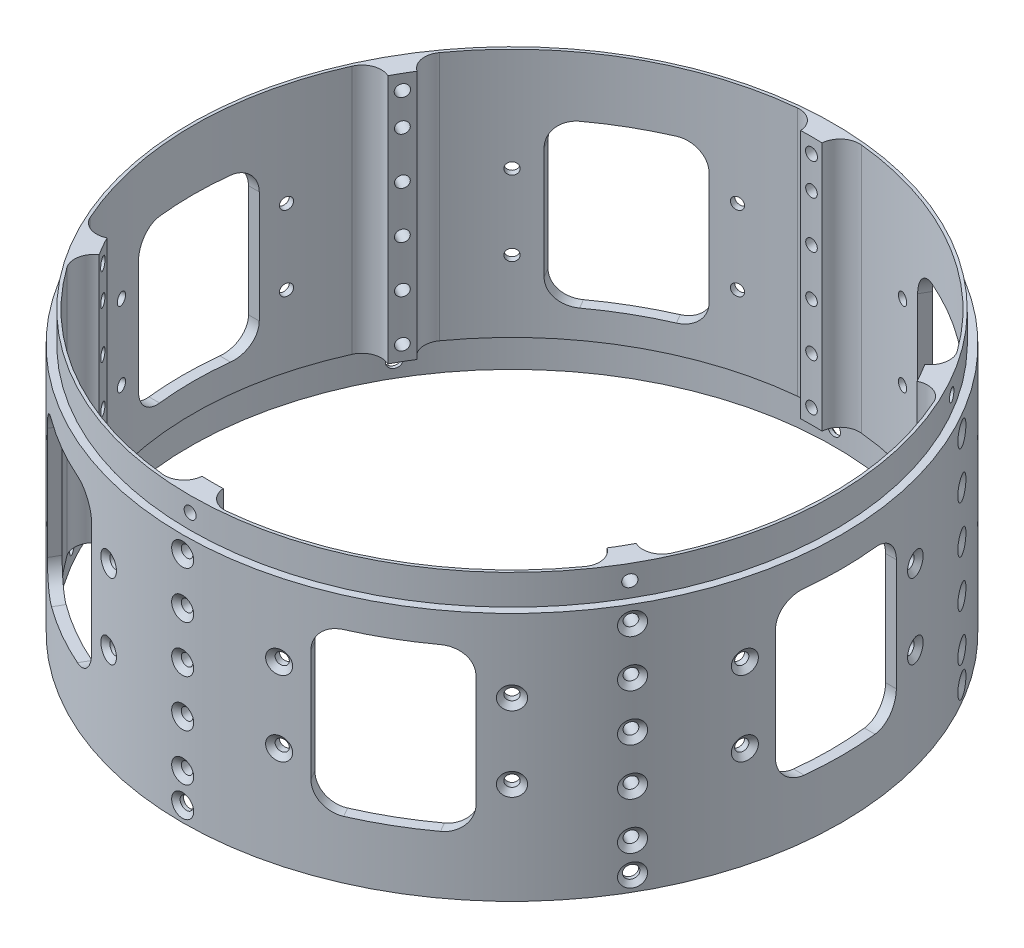
SolidWorks part; units mm, degrees
material "6061-T6 (SS)"
ref_plane "Front Plane" through (0, 0, 0) normal (0, 0, 1) x (1, 0, 0)
ref_plane "Top Plane" through (0, 0, 0) normal (0, 1, 0) x (1, 0, 0)
ref_plane "Right Plane" through (0, 0, 0) normal (1, 0, 0) x (0, 0, -1)
sketch "Sketch1" plane through (0, 0, 0) normal (0, 0, 1) x (1, 0, 0)
  line L0 (0, 42.3951) -> (0, -32.8937) construction
  line L1 (0, -35.6235) -> (0, 35.6235) construction
  line L2 (76.2, -63.5) -> (76.2, 0)
  line L3 (76.2, 0) -> (81.8896, 0)
  line L4 (81.8896, 0) -> (81.8896, -7.6708)
  line L5 (81.8896, -7.6708) -> (83.82, -7.6708)
  line L6 (83.82, -7.6708) -> (83.82, -71.12)
  line L7 (83.82, -71.12) -> (81.9404, -71.12)
  line L8 (81.9404, -71.12) -> (81.9404, -63.5)
  line L9 (81.9404, -63.5) -> (76.2, -63.5)
  line L10 (81.8896, -7.62) -> (84.2911, -7.62) construction
  dimension "D5" = 5.6896
  dimension "D10" = 76.2
  dimension "D2" = 7.62
  dimension "D4" = 7.62
  dimension "D6" = 7.62
revolve "Revolve1" add sketch "Sketch1" angle 360 about L0
sketch "Sketch2" plane through (0, 0, 0) normal (0, 1, 0) x (1, 0, 0)
  line L0 (0, 0) -> (0, 112.6688) construction
  line L1 (0, -35.6235) -> (0, 35.6235) construction
  line L2 (0, 0) -> (-128.6689, 74.287) construction
  line L3 (0, 0) -> (-50.2561, 87.0461) construction
  line L4 (0, 0) -> (-7.6343, 75.8166) construction
  arc A0 (-7.6343, 75.8166) -> (-61.8419, 44.5198) centre (0, 0) ccw construction
  arc A1 (-8.128, 80.7194) -> (-65.841, 47.3988) centre (0, 0) ccw
  arc A2 (-7.1406, 70.9138) -> (-57.8428, 41.6409) centre (0, 0) ccw
  arc A3 (-7.1406, 70.9138) -> (-8.128, 80.7194) centre (-7.6343, 75.8166) ccw
  arc A4 (-65.841, 47.3988) -> (-57.8428, 41.6409) centre (-61.8419, 44.5198) ccw
  circle A5 centre (0, 0) radius 81.8896 construction
  circle A7 centre (0, 0) radius 76.2 construction
  point P5 (-38.1, 65.9911)
  dimension "D2" = 0.762
  dimension "D1" = 60
  dimension "D3" = 30
  dimension "D4" = 5.75
extrude "Cut-Extrude1" cut sketch "Sketch2" against normal through all
pattern_circular "CirPattern1" count 6 over 360 about axis through (0, 42.3951, 0) along (0, 1, 0) of "Cut-Extrude1"
ref_plane "Plane1" through (0, 0, 83.82) normal (0, 0, 1) x (1, 0, 0)
hole_wizard "Tapped Hole for #4-40 Helicoil1" positions "Sketch3" profile "Sketch4" tap size "#4-40" standard "Helicoil® Inch"
sketch "Sketch3" plane through (0, 0, 83.82) normal (0, 0, 1) x (1, 0, 0)
  line L0 (81.8896, 0) -> (-81.8896, 0) construction
  line L1 (2.7181, 0) -> (-2.7181, 0) construction
  line L2 (2.7181, 0) -> (-2.7181, 0) construction
  line L3 (0, 0) -> (0, -3.81) construction
  line L5 (-2.7181, -63.5) -> (2.7181, -63.5) construction
  line L6 (-2.7181, -63.5) -> (2.7181, -63.5) construction
  line L7 (0, -63.5) -> (0, -59.69) construction
  point P0 (0, -3.81)
  point P21 (0, 0)
  dimension "D1" = 3.81
  dimension "D2" = 3.81
cosmetic thread "Hole Thread6" parameters "D1"=3.556, "D2"=3.7414
sketch "Sketch4" plane through (0, -3.81, 83.82) normal (1, 0, 0) x (0, -1, 0)
  line L0 (0, 0) -> (0, 26.3157)
  line L1 (0, 26.3157) -> (1.524, 25.4)
  line L2 (1.524, 25.4) -> (1.524, 0)
  line L5 (1.524, 0) -> (0, 0)
  line L10 (0, 26.3157) -> (-1.524, 25.4) construction
  line L11 (0, -6.35) -> (0, 107.95) construction
  dimension "Tap Drill Dia." = 3.048
  dimension "Tap Drill Depth" = 25.4
  dimension "Drill Angle" = 118
hole_wizard "CSK for #4 Flat Head Machine Screw (100)1" positions "Sketch5" profile "Sketch6" countersink size "#4" standard "ANSI Inch"
sketch "Sketch5" plane through (0, 0, 83.82) normal (0, 0, 1) x (1, 0, 0)
  line L0 (-2.7181, -63.5) -> (2.7181, -63.5) construction
  line L1 (-2.7181, -63.5) -> (2.7181, -63.5) construction
  line L2 (0, -63.5) -> (0, -67.31) construction
  point P0 (0, -67.31)
  dimension "D1" = 3.81
sketch "Sketch6" plane through (0, -67.31, 83.82) normal (1, 0, 0) x (0, -1, 0)
  line L0 (0, 0) -> (0, 26.3806)
  line L1 (0, 26.3806) -> (1.6319, 25.4)
  line L2 (1.6319, 25.4) -> (1.6319, 1.0284)
  line L3 (1.6319, 1.0284) -> (2.8575, 0)
  line L5 (2.8575, 0) -> (0, 0)
  line L6 (-1.6319, 1.0284) -> (-2.8575, 0) construction
  line L10 (0, 26.3806) -> (-1.632, 25.4) construction
  line L11 (0, -6.35) -> (0, 107.95) construction
  dimension "Hole Dia." = 3.2639
  dimension "Hole Depth" = 25.4
  dimension "Near C'Sink Dia." = 5.715
  dimension "Near C'Sink Angle" = 100
  dimension "Drill Angle" = 118
hole_wizard "CSK for #4 Flat Head Machine Screw (100)3" positions "Sketch12" profile "Sketch13" countersink size "#4" standard "ANSI Inch"
sketch "Sketch12" plane through (0, 0, 83.82) normal (0, 0, 1) x (1, 0, 0)
  line L0 (-2.7181, -63.5) -> (2.7181, -63.5) construction
  line L3 (0, 0) -> (0, -63.5) construction
  line L5 (2.7181, 0) -> (-2.7181, 0) construction
  line L6 (-7.6411, -35.814) -> (7.6411, -35.814) construction
  point P19 (0, -35.814)
  point P68 (0, -47.752)
  point P69 (0, -59.69)
  point P74 (0, -11.938)
  point P75 (0, -23.876)
  dimension "D1" = 27.686
  dimension "D2" = 3
  dimension "D3" = 3.81
other "AlignGroup1"
sketch "Sketch13" plane through (0, -35.814, 83.82) normal (1, 0, 0) x (0, -1, 0)
  line L0 (0, 0) -> (0, 26.2852)
  line L1 (0, 26.2852) -> (1.4732, 25.4)
  line L2 (1.4732, 25.4) -> (1.4732, 1.1616)
  line L3 (1.4732, 1.1616) -> (2.8575, 0)
  line L5 (2.8575, 0) -> (0, 0)
  line L6 (-1.4732, 1.1616) -> (-2.8575, 0) construction
  line L10 (0, 26.2852) -> (-1.4732, 25.4) construction
  line L11 (0, -6.35) -> (0, 107.95) construction
  dimension "Hole Dia." = 2.9464
  dimension "Hole Depth" = 25.4
  dimension "Near C'Sink Dia." = 5.715
  dimension "Near C'Sink Angle" = 100
  dimension "Drill Angle" = 118
pattern_circular "CirPattern2" count 6 over 360 about axis through (0, 42.3951, 0) along (0, 1, 0) of "Tapped Hole for #4-40 Helicoil1", "CSK for #4 Flat Head Machine Screw (100)1", "CSK for #4 Flat Head Machine Screw (100)3"
sketch "Sketch7" plane through (0, 0, 0) normal (1, 0, 0) x (0, 0, -1)
  line L1 (-9.017, -15.24) -> (9.017, -15.24)
  line L2 (-15.367, -21.59) -> (-15.367, -50.038)
  line L3 (-9.017, -56.388) -> (9.017, -56.388)
  line L4 (15.367, -21.59) -> (15.367, -50.038)
  line L5 (-15.367, -15.24) -> (15.367, -56.388) construction
  line L6 (-15.367, -56.388) -> (15.367, -15.24) construction
  arc A0 (-15.367, -50.038) -> (-9.017, -56.388) centre (-9.017, -50.038) ccw
  arc A1 (9.017, -56.388) -> (15.367, -50.038) centre (9.017, -50.038) ccw
  arc A2 (15.367, -21.59) -> (9.017, -15.24) centre (9.017, -21.59) ccw
  arc A3 (-9.017, -15.24) -> (-15.367, -21.59) centre (-9.017, -21.59) ccw
  point P0 (0, -35.814)
  dimension "D4" = 6.35
  dimension "D1" = 41.148
  dimension "D2" = 30.734
  dimension "D3" = 15.24
extrude "Cut-Extrude2" cut sketch "Sketch7" against normal through all
sketch "Sketch9" plane through (0, -7.6708, 0) normal (0, 1, 0) x (1, 0, 0)
  line L0 (-49.5, 0) -> (-83.82, 0)
  line L1 (-50.2347, -13.4603) -> (-80.9639, -21.6942)
  line L2 (-83.82, 11.0351) -> (-83.82, -11.0351) construction
  line L3 (-83.82, -11.0351) -> (-78.1078, -32.3533) construction
  arc A0 (-83.3336, 9.017) -> (-83.3336, -9.017) centre (0, 0) ccw construction
  circle A1 centre (0, 0) radius 83.82 construction
  dimension "D1" = 15
ref_plane "Plane3" through (-80.9639, -7.6708, 21.6942) normal (-0.9659, 0, 0.2588) x (0.2588, 0, 0.9659)
hole_wizard "CSK for #4 Flat Head Machine Screw (100)2" positions "Sketch10" profile "Sketch11" countersink size "#4" standard "ANSI Inch"
sketch "Sketch10" plane through (-80.9639, -7.6708, 21.6942) normal (-0.9659, 0, 0.2588) x (0.2588, 0, 0.9659)
  line L0 (0, 0) -> (0, -18.6182) construction
  line L1 (0, -18.6182) -> (0, -37.6682) construction
  line L5 (0, -28.1432) -> (-6.4831, -28.1432) construction
  line L8 (-6.4831, -13.9192) -> (-6.4831, -42.3672) construction
  point P0 (0, -18.6182)
  point P2 (0, -37.6682)
  dimension "D1" = 19.05
sketch "Sketch11" plane through (-80.9639, -26.289, 21.6942) normal (0, 1, 0) x (0.2588, 0, 0.9659)
  line L0 (0, 0) -> (0, 26.2852)
  line L1 (0, 26.2852) -> (1.4732, 25.4)
  line L2 (1.4732, 25.4) -> (1.4732, 1.1616)
  line L3 (1.4732, 1.1616) -> (2.8575, 0)
  line L5 (2.8575, 0) -> (0, 0)
  line L6 (-1.4732, 1.1616) -> (-2.8575, 0) construction
  line L10 (0, 26.2852) -> (-1.4732, 25.4) construction
  line L11 (0, -6.35) -> (0, 107.95) construction
  dimension "Hole Dia." = 2.9464
  dimension "Hole Depth" = 25.4
  dimension "Near C'Sink Dia." = 5.715
  dimension "Near C'Sink Angle" = 100
  dimension "Drill Angle" = 118
mirror "Mirror1" about plane through (0, 0, 0) normal (0, 0, 1) of "CSK for #4 Flat Head Machine Screw (100)2"
pattern_circular "CirPattern5" count 6 over 360 about axis through (0, -7.6708, 0) along (0, 1, 0) of "Cut-Extrude2", "Mirror1"
ref_plane "Plane2" [suppressed] through (0, 0, 0) normal (-0.7071, 0, 0.7071) x (0.7071, 0, 0.7071)
sketch "Sketch8" [suppressed] plane through (0, 0, 0) normal (-0.7071, 0, 0.7071) x (0.7071, 0, 0.7071)
  line L0 (0, 0) -> (89.1919, 0) construction
  line L1 (-9.017, -17.145) -> (-6.858, -17.145)
  line L2 (-12.192, -20.32) -> (-12.192, -31.115)
  line L3 (-9.017, -34.29) -> (-6.858, -34.29)
  line L4 (-3.683, -20.32) -> (-3.683, -31.115)
  line L5 (0, 0) -> (0, -89.2767) construction
  line L6 (-83.82, -71.12) -> (83.82, -71.12) construction
  line L7 (-7.9375, -52.07) -> (-4.7625, -52.07)
  line L8 (-9.525, -53.6575) -> (-9.525, -56.8325)
  line L9 (-7.9375, -58.42) -> (-4.7625, -58.42)
  line L10 (-3.175, -53.6575) -> (-3.175, -56.8325)
  arc A0 (-9.017, -34.29) -> (-12.192, -31.115) centre (-9.017, -31.115) cw
  arc A1 (-3.683, -31.115) -> (-6.858, -34.29) centre (-6.858, -31.115) cw
  arc A2 (-3.683, -20.32) -> (-6.858, -17.145) centre (-6.858, -20.32) ccw
  arc A3 (-9.017, -17.145) -> (-12.192, -20.32) centre (-9.017, -20.32) ccw
  arc A4 (-9.525, -56.8325) -> (-7.9375, -58.42) centre (-7.9375, -56.8325) ccw
  arc A5 (-3.175, -56.8325) -> (-4.7625, -58.42) centre (-4.7625, -56.8325) cw
  arc A6 (-3.175, -53.6575) -> (-4.7625, -52.07) centre (-4.7625, -53.6575) ccw
  arc A7 (-7.9375, -52.07) -> (-9.525, -53.6575) centre (-7.9375, -53.6575) ccw
  circle A8 centre (-6.35, -48.895) radius 1.5875
  circle A9 centre (-6.35, -61.595) radius 1.5875
  point P20 (-3.175, -55.245)
  point P29 (-6.35, -58.42)
  dimension "D1" = 3.175
  dimension "D8" = 1.5875
  dimension "D11" = 3.175
  dimension "D12" = 3.175
  dimension "D2" = 8.509
  dimension "D3" = 17.145
  dimension "D4" = 17.145
  dimension "D5" = 3.683
  dimension "D6" = 6.35
  dimension "D7" = 6.35
  dimension "D9" = 6.35
  dimension "D10" = 12.7
  dimension "D13" = 3.175
  dimension "D14" = 3.175
extrude "Cut-Extrude3" [suppressed] cut sketch "Sketch8" along normal through all
equation "\"nominalLength\"=2.5"
equation "\"D8@Sketch1\"=\"nominalLength\""
equation "\"D12@Sketch8\"=\"D11@Sketch8\""
